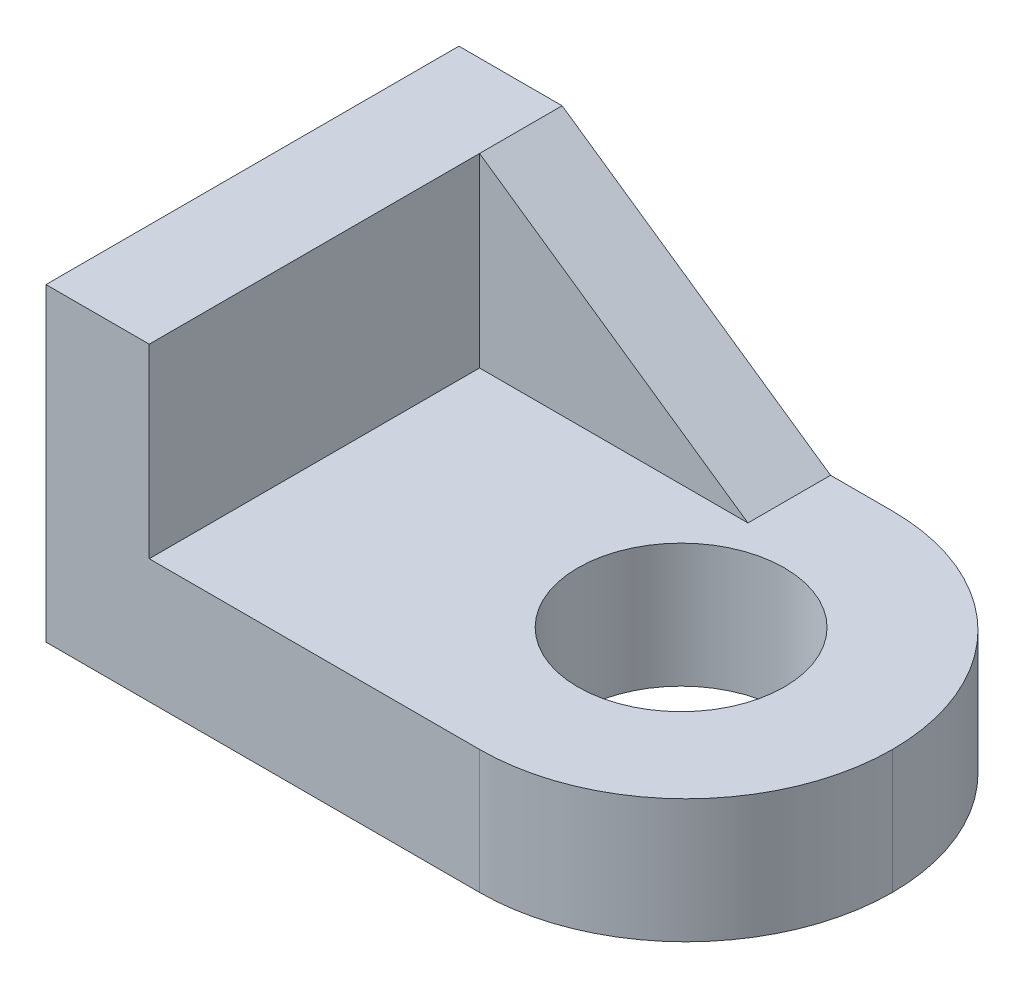
SolidWorks part; units mm, degrees
ref_plane "前基準面" through (0, 0, 0) normal (0, 0, 1) x (1, 0, 0)
ref_plane "上基準面" through (0, 0, 0) normal (0, 1, 0) x (1, 0, 0)
ref_plane "右基準面" through (0, 0, 0) normal (1, 0, 0) x (0, 0, -1)
sketch "草圖1" plane through (0, 0, 0) normal (0, 0, 1) x (1, 0, 0)
  line L0 (0, 0) -> (0, 30)
  line L1 (0, 30) -> (10, 30)
  line L2 (10, 30) -> (10, 12)
  line L3 (10, 12) -> (62, 12)
  line L4 (62, 12) -> (62, 0)
  line L5 (62, 0) -> (0, 0)
  dimension "D1" = 62
  dimension "D2" = 12
  dimension "D3" = 10
  dimension "D4" = 30
extrude "填料-伸長1" add sketch "草圖1" along normal mid plane 40
fillet "圓角1" radius 20 2 edges at (62, 6, -20) (62, 6, 20)
sketch "草圖2" plane through (0, 12, 0) normal (0, 1, 0) x (1, 0, 0)
  line L2 (0, 0) -> (65.5519, 0) construction
  line L3 (42, -20) -> (10, -20) construction
  line L4 (42, 20) -> (10, 20) construction
  circle A0 centre (41.5242, 0) radius 10
  dimension "D1" = 20
extrude "除料-伸長1" cut sketch "草圖2" against normal through all
sketch "草圖4" plane through (0, 0, -20) normal (0, 0, -1) x (-1, 0, 0)
  line L0 (-10, 30) -> (-36, 12)
  line L1 (-42, 12) -> (-10, 12) construction
  line L2 (-36, 12) -> (-10, 12)
  line L3 (-10, 12) -> (-10, 30)
  dimension "D1" = 26
extrude "填料-伸長2" add sketch "草圖4" against normal blind 8
